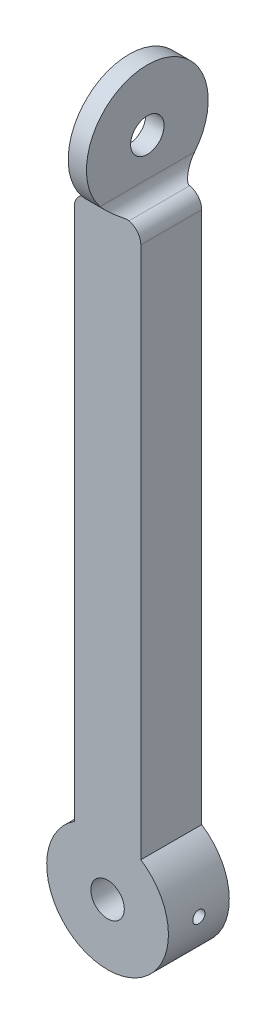
SolidWorks part; units mm, degrees
ref_plane "Front Plane" through (0, 0, 0) normal (0, 0, 1) x (1, 0, 0)
ref_plane "Top Plane" through (0, 0, 0) normal (0, 1, 0) x (1, 0, 0)
ref_plane "Right Plane" through (0, 0, 0) normal (1, 0, 0) x (0, 0, -1)
sketch "Sketch2" plane through (0, 0, 0) normal (0, 0, 1) x (1, 0, 0)
  line L0 (282.7658, 340.4915) -> (282.7658, 224.5508) construction
  line L1 (282.7658, 96.9612) -> (508.2568, 96.9612) construction
  line L2 (288.2295, 213.4254) -> (288.2295, 123.4254)
  line L3 (277.3021, 213.4254) -> (277.3021, 123.4254)
  line L4 (277.3021, 213.4254) -> (288.2295, 213.4254)
  line L5 (282.7658, 219.0508) -> (282.7658, 96.9612) construction
  line L7 (282.7658, 115.05) -> (297.3206, 115.05) construction
  arc A2 (277.3021, 123.4254) -> (288.2295, 123.4254) centre (282.7658, 115.05) ccw
  circle A3 centre (282.7658, 115.05) radius 2.75
  point P6 (282.7658, 115.05)
  dimension "D2" = 282.7658
  dimension "D4" = 20
  dimension "D5" = 5.5
  dimension "D1" = 90
extrude "Boss-Extrude1" add sketch "Sketch2" along normal blind 10
sketch "Sketch3" plane through (0, 0, 0) normal (1, 0, 0) x (0, 0, -1)
  line L0 (-10, 213.4254) -> (0, 213.4254) construction
  circle A0 centre (-5, 222.0856) radius 10
  circle A1 centre (-5, 222.0856) radius 2.75
  point P4 (-5, 213.4254)
  dimension "D1" = 20
  dimension "D2" = 5.5
extrude "Boss-Extrude2" add sketch "Sketch3" along normal blind 1.5 and the other way blind 1.5 from offset 282.8
fillet "Fillet2" radius 2.5 1 edges at (277.3021, 213.4254, 5)
fillet "Fillet3" radius 2.5 1 edges at (288.2295, 213.4254, 5)
fillet "Fillet4" radius 2.5 1 edges at (284.3, 213.4254, 5)
fillet "Fillet5" radius 2.5 1 edges at (281.3, 213.4254, 5)
sketch "Sketch5" plane through (0, 0, 10) normal (0, 0, 1) x (1, 0, 0)
  line L0 (282.7658, 115.05) -> (285.5158, 115.05) construction
  circle A0 centre (282.7658, 115.05) radius 2.75 construction
sketch "Sketch6" plane through (0, 0, 0) normal (0, 0, -1) x (-1, 0, 0)
  point P0 (-282.7658, 115.05)
sketch3d "3DSketch1"
  line L0 (282.7658, 115.05, 0) -> (282.7658, 115.05, 10) construction
sketch "Sketch7" plane through (277.3021, 0, 0) normal (-1, 0, 0) x (0, 0, 1)
  line L0 (5, 123.4254) -> (5, 105.05) construction
  line L1 (10, 123.4254) -> (0, 123.4254) construction
  line L2 (0, 105.05) -> (10, 105.05) construction
sketch "Sketch10" plane through (277.3021, 0, 0) normal (-1, 0, 0) x (0, 0, 1)
  line L0 (0, 115.05) -> (10, 115.05) construction
  circle A0 centre (5, 115.05) radius 1
  dimension "D1" = 2
extrude "Cut-Extrude3" cut sketch "Sketch10" against normal through all both and the other way through all
